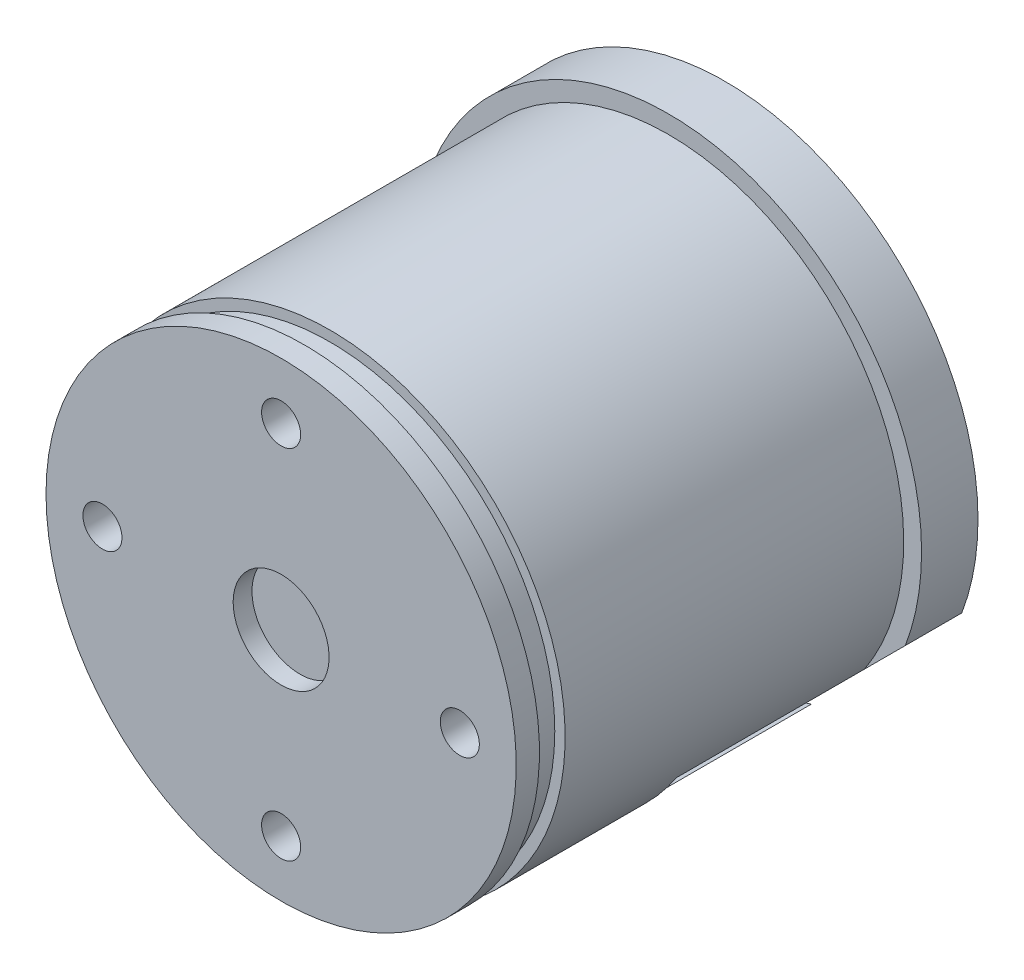
SolidWorks part; units mm, degrees
ref_plane "Front Plane" through (0, 0, 0) normal (0, 0, 1) x (1, 0, 0)
ref_plane "Top Plane" through (0, 0, 0) normal (0, 1, 0) x (1, 0, 0)
ref_plane "Right Plane" through (0, 0, 0) normal (1, 0, 0) x (0, 0, -1)
ref_axis "Z" through (0, 0, 21.88) along (0, 0, -1)
ref_plane "Plane1" through (0, 0, 0) normal (0.7071, 0.7071, 0) x (0, 0, -1)
sketch "Sketch10" plane through (0, 0, 0) normal (0, 1, 0) x (1, 0, 0)
  line L0 (-13.45, 3) -> (0, 3)
  line L1 (0, 38.469) -> (0, 33.6342) construction
  line L2 (0, -21.88) -> (0, 6.28) construction
  line L3 (-13.45, 3) -> (-13.45, 0)
  line L4 (-13.45, 0) -> (-12.5, 0)
  line L5 (-12.5, 0) -> (-12.5, -18)
  line L6 (-12.5, -18) -> (-11.95, -18)
  line L7 (-11.95, -18) -> (-11.95, -19.365)
  line L8 (-11.95, -19.365) -> (-12.5, -19.365)
  line L9 (-12.5, -19.365) -> (-12.5, -20.6)
  line L10 (-12.5, -20.6) -> (-2.55, -20.6)
  line L11 (-2.55, -20.6) -> (-2.55, -19.6)
  line L12 (-2.55, -19.6) -> (0, -19.6)
  line L13 (0, -19.6) -> (0, 3)
  dimension "D1" = 25
  dimension "D2" = 26.9
  dimension "D4" = 3
  dimension "D3" = 20.6
  dimension "D5" = 18
  dimension "D6" = 1.365
  dimension "D7" = 23.9
  dimension "D8" = 1
  dimension "D9" = 5.1
revolve "Revolve1" add sketch "Sketch10" angle 360 about L1
sketch "Sketch11" plane through (0, 0, 0) normal (0, 0, 1) x (1, 0, 0)
  line L0 (9.5, 0) -> (0, 0) construction
  circle A0 centre (9.5, 0) radius 1.0386
  point P3 (0, 0)
  dimension "D1" = 9.5
extrude "Cut-Extrude1" cut sketch "Sketch11" against normal through all both and the other way through all
pattern_circular "CirPattern1" count 4 over 360 about axis through (0, 0, 21.88) along (0, 0, -1) of "Cut-Extrude1"
sketch "Sketch14" plane through (0, 0, 0) normal (0, 0, 1) x (1, 0, 0)
  line L0 (0, 0) -> (8.8388, -8.8388) construction
  line L2 (8.8388, -8.8388) -> (17.6777, 0) construction
  line L3 (2.7236, -7.4831) -> (0, 0) construction
  line L4 (0, 0) -> (-4.6648, 0) construction
  line L5 (2.4887, -7.5686) -> (-0.2349, -0.0855)
  line L6 (9.0156, -9.0156) -> (17.8544, -0.1768)
  line L7 (8.6621, -8.6621) -> (17.5009, 0.1768)
  line L8 (2.9586, -7.3976) -> (0.2349, 0.0855)
  line L9 (17.8544, -0.1768) -> (17.5009, 0.1768)
  line L13 (-0.2349, -0.0855) -> (0.2349, 0.0855)
  arc A1 (8.8388, -8.8388) -> (2.7236, -7.4831) centre (6.2131, -6.2131) cw construction
  arc A2 (9.0156, -9.0156) -> (2.4887, -7.5686) centre (6.2131, -6.2131) cw
  arc A3 (8.6621, -8.6621) -> (2.9586, -7.3976) centre (6.2131, -6.2131) cw
  spline S0 degree 4 poles (-1.2346, 0.1956) (-1.1594, 0.1712) (-1.0456, 0.1376) (-0.8922, 0.0988) (-0.699, 0.0605) (-0.5436, 0.036) (-0.3885, 0.0177) (-0.2392, 0.0056) (-0.0583, -0.0003) (0.0419, -0.0006) (0.2016, 0.0042) (0.3388, 0.0133) (0.4703, 0.027) (0.604, 0.0451) (0.7704, 0.0735) (0.9678, 0.1164) (1.1954, 0.1792) (1.45, 0.268) (1.6984, 0.3733) (1.9393, 0.4945) (2.2303, 0.6648) (2.5062, 0.859) (2.869, 1.1613) (3.2868, 1.603) (3.6431, 2.0971) (3.957, 2.6954) (4.1746, 3.2624) (4.3191, 3.7825) (4.4324, 4.4059) (4.4884, 5.173) (4.4459, 5.942) (4.3132, 6.6995) (4.1345, 7.3498) (3.9563, 7.859) (3.6924, 8.4793) (3.313, 9.195) (2.8641, 9.8691) (2.3956, 10.4455) (2.0309, 10.8412) (1.7446, 11.1295) (1.4543, 11.4041) (1.1404, 11.6736) (0.8355, 11.9175) (0.5472, 12.1296) (0.3617, 12.2629) (0.0858, 12.4456) (-0.0439, 12.5287) (-0.2722, 12.6693) (-0.4394, 12.767) (-0.6227, 12.8706) (-0.8036, 12.9685) (-0.9875, 13.064) (-1.1725, 13.1561) (-1.3126, 13.2229) (-1.4064, 13.2663) (-1.4535, 13.2878) knots 0 0 0 0 0 0.016254 0.024381 0.032508 0.04051 0.048511 0.056512 0.064513 0.071439 0.078366 0.085293 0.092219 0.099146 0.106072 0.119925 0.133778 0.147631 0.161484 0.175337 0.18919 0.216896 0.23075 0.272309 0.313868 0.341574 0.36928 0.396986 0.424692 0.471658 0.52707 0.554776 0.582483 0.610189 0.637895 0.693307 0.748719 0.776425 0.790278 0.804131 0.831837 0.859543 0.873397 0.88725 0.901103 0.914956 0.925586 0.936217 0.946847 0.957478 0.968108 0.978739 0.989369 1 1 1 1 1 construction
  spline S1 degree 4 poles (0, 0) (0.0287, 0) (0.0863, 0.0008) (0.2016, 0.0042) (0.3388, 0.0133) (0.4703, 0.027) (0.604, 0.0451) (0.7704, 0.0735) (0.9678, 0.1164) (1.1954, 0.1792) (1.45, 0.268) (1.6984, 0.3733) (1.9393, 0.4945) (2.2303, 0.6648) (2.5062, 0.859) (2.869, 1.1613) (3.2868, 1.603) (3.6431, 2.0971) (3.957, 2.6954) (4.1746, 3.2624) (4.3191, 3.7825) (4.4324, 4.4059) (4.4884, 5.173) (4.4459, 5.942) (4.3132, 6.6995) (4.1345, 7.3498) (3.9563, 7.859) (3.6924, 8.4793) (3.313, 9.195) (2.8641, 9.8691) (2.3956, 10.4455) (2.0309, 10.8412) (1.7446, 11.1295) (1.4543, 11.4041) (1.1404, 11.6736) (0.8355, 11.9175) (0.5472, 12.1296) (0.3617, 12.2629) (0.142, 12.4084) (0.0483, 12.4692) (0, 12.5) knots 0.064513 0.064513 0.064513 0.064513 0.064513 0.071439 0.078366 0.085293 0.092219 0.099146 0.106072 0.119925 0.133778 0.147631 0.161484 0.175337 0.18919 0.216896 0.23075 0.272309 0.313868 0.341574 0.36928 0.396986 0.424692 0.471658 0.52707 0.554776 0.582483 0.610189 0.637895 0.693307 0.748719 0.776425 0.790278 0.804131 0.831837 0.859543 0.873397 0.88725 0.901103 0.914956 0.914956 0.914956 0.914956 0.914956 construction
  dimension "D1" = 12.5
  dimension "D3" = 45
  dimension "D2" = 70
  dimension "D4" = 0.25
  dimension "D5" = 0.25
extrude "Cut-Extrude2" cut sketch "Sketch14" against normal through all and the other way blind 10
sketch "Sketch15" plane through (0, 0, 0) normal (0, 0, 1) x (1, 0, 0)
  line L0 (13.8414, -3.4827) -> (4.053, -13.2711)
  line L1 (4.053, -13.2711) -> (6.247, -15.4651)
  line L2 (6.247, -15.4651) -> (16.0354, -5.6767)
  line L3 (16.0354, -5.6767) -> (13.8414, -3.4827)
  line L4 (10.421, -6.9032) -> (12.5889, -4.7352) construction
  point P6 (6.247, -15.4651)
extrude "Cut-Extrude3" cut sketch "Sketch15" against normal through all
equation "\"BearingBaseDistance\"= 10"
equation "\"BearingOD\"= 32"
equation "\"BearingHeight\"= 4"
equation "\"SeatsOD\"= \"BearingOD\" + 10"
equation "\"WireHarnessHeight\"= 4"
equation "\"OuterWallWidth\"= 6"
equation "\"OverallOD\" = 45"
equation "\"RetainingRingThickness\" = 1.30"
equation "\"RetaininRingGrooveDiameter\" = 23.9"
equation "\"ShaftLengthAfterFlange\" = 2*\"BearingHeight\" + \"BearingBaseDistance\" + \"RetainingRingThickness\"*2\t'give a retaining ring thickness of extra clearance"
equation "\"RetainingRingGrooveBase\" = \"ShaftLengthAfterFlange\" - \"RetainingRingThickness\"*2"
equation "\"BearingID\" = 25"
equation "\"CoverClearance\" = 1"
equation "\"CoverThickness\" = 1"
equation "\"FlangHeight\" = 3"
equation "\"OuterHousingHeight\" = \"WireHarnessHeight\" + \"BearingHeight\"*2 + \"BearingBaseDistance\""
equation "\"PCBWidth\" = 5"
equation "\"PCBHeight\" = \"OuterHousingHeight\" "
equation "\"PCBThickness\" = 1"
equation "\"NormalDistSidewallPCBToZ\" = (\"OverallOD\"/2) - 1.6\t'radial distance from the z axis to pcb origin on the top/connector side"
equation "\"PCBSidewallCutoutClearance\" = 0.1"
equation "\"OutputHubBoltCircleRadius\" = 8"
equation "\"OutputHubOD\" = 27"
equation "\"StatorWireRadius\" = \"NormalDistSidewallPCBToZ\" - 5.7"
equation "\"MountingHoleRadius\" = (\"OverallOD\"+\"BearingOD\")/4"
equation "\"D1@Sketch10\"=\"BearingID\""
equation "\"BearingInnerRaceOD\" = 26.9"
equation "\"D2@Sketch10\"=\"BearingInnerRaceOD\""
equation "\"D4@Sketch10\"=\"FlangHeight\""
equation "\"D3@Sketch10\"=\"ShaftLengthAfterFlange\""
equation "\"D5@Sketch10\"=\"RetainingRingGrooveBase\""
equation "\"D6@Sketch10\"=\"RetainingRingThickness\"*1.05"
equation "\"D7@Sketch10\"=\"RetaininRingGrooveDiameter\""
equation "\"D1@Sketch11\"=round(\"BearingID\"*0.75)/2"
equation "\"D1@Sketch14\"=\"BearingID\"/2"
